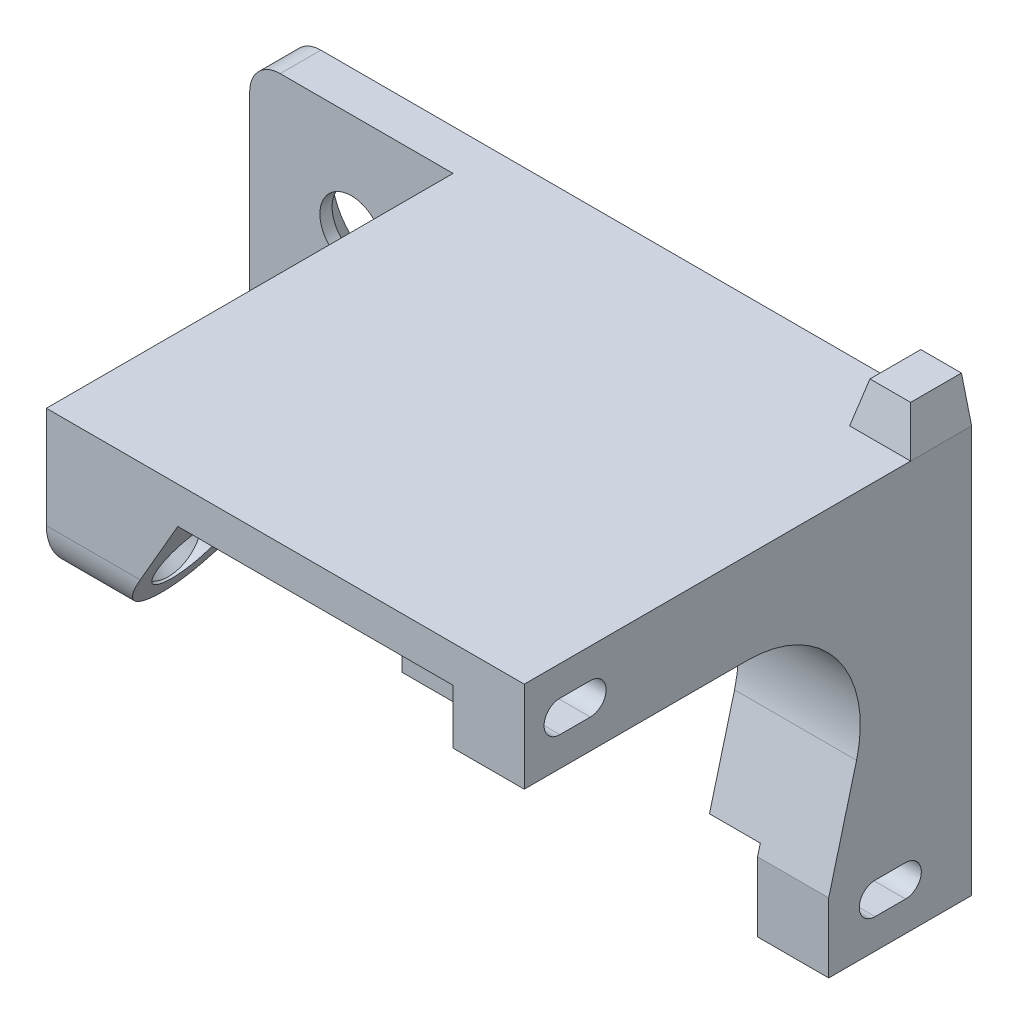
SolidWorks part; units mm, degrees
ref_plane "Front Plane" through (0, 0, 0) normal (0, 0, 1) x (1, 0, 0)
ref_plane "Top Plane" through (0, 0, 0) normal (0, 1, 0) x (1, 0, 0)
ref_plane "Right Plane" through (0, 0, 0) normal (1, 0, 0) x (0, 0, -1)
sketch "Sketch1" plane through (0, 0, 0) normal (0, 0, 1) x (1, 0, 0)
  line L0 (-10, -20) -> (-10, 0) construction
  line L1 (-10, -20) -> (10, -20) construction
  line L2 (-10, 0) -> (10, 0) construction
  line L3 (10, -20) -> (10, 0) construction
  line L4 (-10, -20) -> (10, 0) construction
  line L5 (-10, 0) -> (10, -20) construction
  line L6 (-10, 0) -> (-10, 20) construction
  line L7 (-10, 17) -> (-10, -17)
  line L8 (-10, 20) -> (10, 20) construction
  line L9 (10, 0) -> (10, 20) construction
  line L10 (-10, 0) -> (10, 20) construction
  line L11 (-10, 20) -> (10, 0) construction
  line L12 (-7, 20) -> (57, 20)
  line L13 (57, 20) -> (57, -20)
  line L14 (57, -20) -> (45, -20)
  line L15 (45, -20) -> (45, -2)
  line L16 (45, -2) -> (38, -2)
  line L17 (10, -20) -> (25, -20)
  line L18 (10, -20) -> (-7, -20)
  line L20 (25, -20) -> (38, -2)
  circle A0 centre (0, 10) radius 3.1
  circle A1 centre (0, -10) radius 3.1
  arc A2 (-7, 20) -> (-10, 17) centre (-7, 17) ccw
  arc A3 (-10, -17) -> (-7, -20) centre (-7, -17) ccw
  point P0 (0, 10)
  point P1 (0, -10)
  dimension "D2" = 6.2
  dimension "D6" = 3
  dimension "D1" = 20
  dimension "D3" = 57
  dimension "D4" = 12
  dimension "D5" = 7
  dimension "D7" = 18
  dimension "D8" = 15
extrude "Boss-Extrude1" add sketch "Sketch1" along normal blind 9
sketch "Sketch2" plane through (0, 0, 9) normal (0, 0, 1) x (1, 0, 0)
  line L0 (57, 20) -> (-7, 20) construction
  line L1 (10, 20) -> (-10, 20)
  line L2 (10, 20) -> (10, -20)
  line L3 (10, -20) -> (-10, -20)
  line L4 (-10, 20) -> (-10, -20)
  line L5 (-10, 20) -> (10, -20) construction
  line L6 (10, 20) -> (-10, -20) construction
  line L7 (-10, 17) -> (-10, -17) construction
  point P6 (0, 0)
extrude "Cut-Extrude1" cut sketch "Sketch2" against normal offset from surface (5 mm away) 4 up to face at (3.1, 10, 0)
sketch "Sketch3" plane through (0, 0, 9) normal (0, 0, 1) x (1, 0, 0)
  line L0 (10, 20) -> (10, -20) construction
  circle A0 centre (28, -8) radius 6.05
  dimension "D2" = 8
  dimension "D3" = 12.1
  dimension "D1" = 18
extrude "Cut-Extrude2" cut sketch "Sketch3" against normal up to surface (5 mm away) up to face at (3.1, 10, 4)
sketch "Sketch4" plane through (0, 0, 9) normal (0, 0, 1) x (1, 0, 0)
  line L0 (45, -20) -> (57, -20)
  line L1 (45, -20) -> (57, -20) construction
  line L2 (57, -20) -> (57, 20) construction
  line L3 (57, -20) -> (57, 20)
  line L4 (57, 20) -> (10, 20)
  line L5 (10, 20) -> (10, 16.4)
  line L6 (10, 20) -> (10, -20) construction
  line L7 (10, 16.4) -> (45, 16.4)
  line L8 (45, 16.4) -> (45, -20)
  dimension "D1" = 3.6
  dimension "D2" = 12
extrude "Boss-Extrude2" add sketch "Sketch4" along normal blind 35
sketch "Sketch5" plane through (0, 0, 9) normal (0, 0, 1) x (1, 0, 0)
  line L0 (38, -2) -> (45, -2) construction
  line L1 (45, -2) -> (38, -2)
  line L2 (45, -2) -> (45, 10)
  line L3 (45, 10) -> (38, 10)
  line L4 (38, -2) -> (38, 10)
  line L5 (34.0291, -7.4981) -> (38, -2) construction
  dimension "D1" = 12
  dimension "D2" = 7
extrude "Cut-Extrude3" cut sketch "Sketch5" against normal offset from surface (6 mm away) 3 up to face at (3.1, 10, 0)
chamfer "Chamfer1" distance 6 distance2 4 1 edges at (41.5, 10, 9) first distance on face at (27.5911, -2.1497, 9)
chamfer "Chamfer2" distance 1 distance2 1 1 edges at (41.5, -2, 3)
sketch "Sketch6" plane through (57, 0, 0) normal (1, 0, 0) x (0, 0, -1)
  line L0 (-22, 0) -> (-22, 20) construction
  line L1 (-44, -20) -> (0, -20) construction
  line L2 (-22, 0) -> (-2, 0) construction
  line L3 (-22, 11.05) -> (-44, 11.05)
  line L4 (-37.5, -15.5) -> (-6.5, -15.5) construction
  line L5 (-6.5, -15.5) -> (-6.5, 15.5) construction
  line L6 (-6.5, 15.5) -> (-37.5, 15.5) construction
  line L7 (-37.5, 15.5) -> (-37.5, -15.5) construction
  line L8 (-44, -20) -> (-44, 20) construction
  line L9 (-44, 11.05) -> (-44, -20)
  line L10 (-44, -20) -> (-14.0556, -20)
  line L11 (-14.0556, -13.1731) -> (-11.3177, -2.8269)
  line L12 (-44, 20) -> (0, 20) construction
  line L13 (-14.0556, -20) -> (-14.0556, -13.1731)
  line L14 (-40.5, 17.05) -> (-37.5, 17.05)
  line L15 (-40.5, 13.95) -> (-37.5, 13.95)
  line L16 (-9.5, -17.05) -> (-6.5, -17.05)
  line L17 (-9.5, -13.95) -> (-6.5, -13.95)
  arc A0 (-11.3177, -2.8269) -> (-22, 11.05) centre (-22, 0) ccw
  circle A1 centre (-22, 0) radius 15.5 construction
  arc A2 (-37.5, 13.95) -> (-37.5, 17.05) centre (-37.5, 15.5) ccw
  arc A3 (-6.5, -17.05) -> (-6.5, -13.95) centre (-6.5, -15.5) ccw
  arc A4 (-9.5, -13.95) -> (-9.5, -17.05) centre (-9.5, -15.5) ccw
  arc A5 (-40.5, 17.05) -> (-40.5, 13.95) centre (-40.5, 15.5) ccw
  dimension "D2" = 22.1
  dimension "D3" = 31
  dimension "D4" = 3.1
  dimension "D1" = 3
  dimension "D5" = 22
  dimension "D6" = 3
extrude "Cut-Extrude4" cut sketch "Sketch6" against normal up to surface (12 mm away) up to face at (45, 2.4, 12)
sketch "Sketch7" plane through (57, 0, 0) normal (1, 0, 0) x (0, 0, -1)
  line L0 (-6.5, -18.85) -> (-6.5, -20)
  line L1 (-14.0556, -20) -> (-14.0556, -12.15)
  line L2 (-6.5, -20) -> (-14.0556, -20)
  line L3 (-37.5, 18.85) -> (-40.5, 18.85)
  line L5 (-14.0556, -12.15) -> (-6.5, -12.15)
  line L6 (-37.5, 12.15) -> (-37.5, 11.05)
  line L7 (-22, 11.05) -> (-44, 11.05) construction
  line L8 (-37.5, 11.05) -> (-44, 11.05)
  line L9 (-44, 11.05) -> (-44, 16.4)
  line L11 (-44, 16.4) -> (-43.1946, 17.4904)
  arc A0 (-37.5, 12.15) -> (-37.5, 18.85) centre (-37.5, 15.5) ccw
  arc A1 (-6.5, -18.85) -> (-6.5, -12.15) centre (-6.5, -15.5) ccw
  circle A2 centre (-37.5, 15.5) radius 1.55 construction
  circle A3 centre (-6.5, -15.5) radius 1.55 construction
  arc A4 (-40.5, 18.85) -> (-43.1946, 17.4904) centre (-40.5, 15.5) ccw
  dimension "D1" = 6.7
extrude "Cut-Extrude5" cut sketch "Sketch7" against normal blind 11 from offset 7 offset against normal yes
chamfer "Chamfer3" [suppressed] distance 1.8 angle 45
chamfer "Chamfer4" [suppressed] distance 7 distance2 2
sketch "Sketch8" plane through (0, 20, 0) normal (0, 1, 0) x (1, 0, 0)
  line L0 (57, -44) -> (57, 0) construction
  line L1 (57, 0) -> (51, 0)
  line L2 (57, 0) -> (57, -6)
  line L3 (57, -6) -> (51, -6)
  line L4 (51, 0) -> (51, -6)
  line L5 (57, 0) -> (-7, 0) construction
  dimension "D1" = 6
extrude "Boss-Extrude3" add sketch "Sketch8" along normal blind 4
chamfer "Chamfer5" distance 4 distance2 1 3 edges at (51, 24, 3) (54, 24, 6) (57, 24, 3) first distance on face at (51, 22, 3) first distance on face at (54, 22, 6) first distance on face at (57, 15.5, 39)
chamfer "Chamfer6" distance 1 distance2 4 1 edges at (38, 7, 9) first distance on face at (27.5911, -1.1497, 9)
chamfer "Chamfer7" distance 2.8 angle 45 2 edges at (3.1, -10, 0) (3.1, 10, 0)
sketch "Sketch9" plane through (10, 0, 0) normal (-1, 0, 0) x (0, 0, 1)
  line L0 (44, 16.4) -> (44, 10)
  line L1 (4, 20) -> (44, 20) construction
  line L2 (35.4645, 6.4645) -> (25.5289, 16.4)
  line L3 (34.2732, 16.4) -> (9, 16.4) construction
  line L4 (25.5289, 16.4) -> (44, 16.4)
  arc A0 (44, 10) -> (35.4645, 6.4645) centre (39, 10) cw
  dimension "D3" = 5
  dimension "D1" = 45
  dimension "D2" = 10
extrude "Boss-Extrude4" add sketch "Sketch9" against normal blind 6
chamfer "Chamfer8" distance 12 angle 30 1 edges at (16, 16.4, 34.7645) first distance on face at (16, 11.6032, 37.5436)
sketch "Sketch10" plane through (10, 0, 0) normal (-1, 0, 0) x (0, 0, 1)
  circle A0 centre (39, 10) radius 1.55
  arc A1 (35.4645, 6.4645) -> (44, 10) centre (39, 10) ccw construction
  dimension "D1" = 3.1
extrude "Cut-Extrude6" cut sketch "Sketch10" against normal up to next
sketch "Sketch11" plane through (10, 0, 0) normal (-1, 0, 0) x (0, 0, 1)
  circle A0 centre (39, 10) radius 3.35
  circle A1 centre (39, 10) radius 1.55 construction
  dimension "D1" = 6.7
extrude "Cut-Extrude7" cut sketch "Sketch11" against normal up to next from offset 7 offset against normal yes
chamfer "Chamfer9" distance 1.8 angle 45 1 edges at (17, 8.45, 39)
